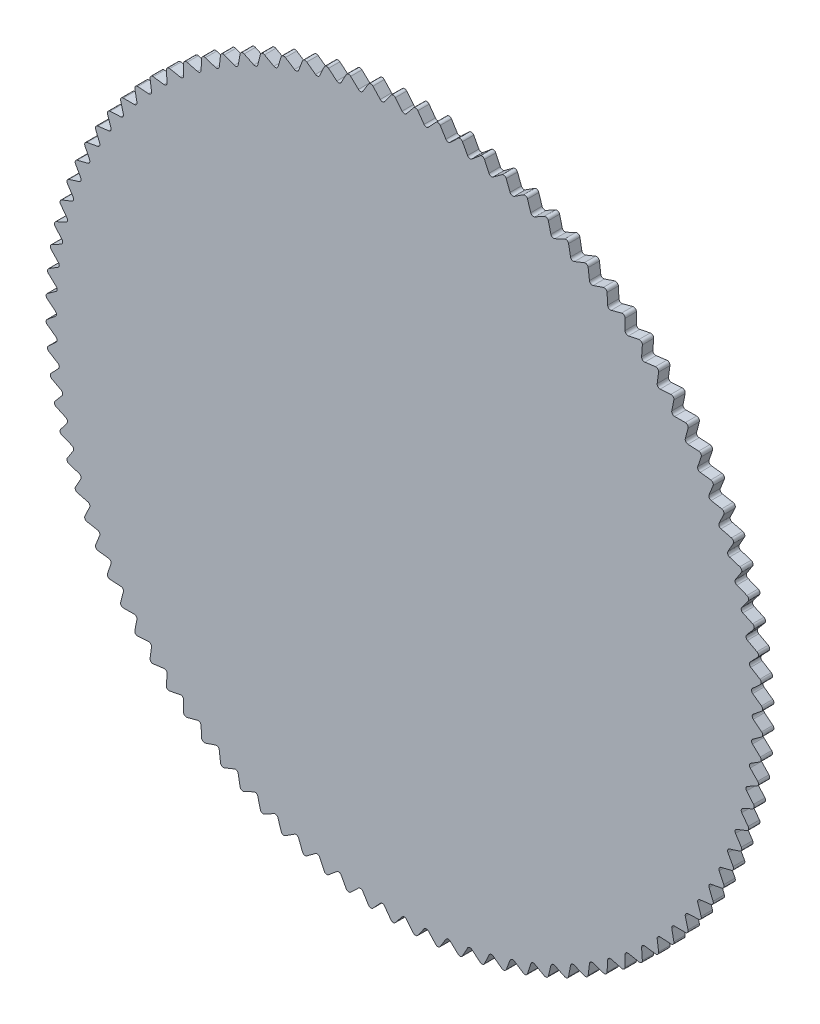
SolidWorks part; units mm, degrees
ref_plane "Front Plane" through (0, 0, 0) normal (0, 0, 1) x (1, 0, 0)
ref_plane "Top Plane" through (0, 0, 0) normal (0, 1, 0) x (1, 0, 0)
ref_plane "Right Plane" through (0, 0, 0) normal (1, 0, 0) x (0, 0, -1)
sketch "Sketch1" plane through (0, 0, 0) normal (0, 0, 1) x (1, 0, 0)
  line L0 (-7.7387, 246.25) -> (7.7387, 246.25) construction
  line L1 (0, 0) -> (0, 246.25) construction
  line L2 (0, 246.25) -> (0, 253.75) construction
  line L5 (-1.5508, 246.9871) -> (-6.3568, 252.8887)
  line L6 (0, 253.75) -> (0, 59.7644) construction
  line L7 (1.5508, 246.9871) -> (6.3568, 252.8887)
  line L8 (0, 0) -> (-7.9705, 253.6248) construction
  line L9 (0, 0) -> (7.9705, 253.6248) construction
  circle A2 centre (0, 0) radius 246.25 construction
  arc A4 (-7.8527, 249.8766) -> (7.8527, 249.8766) centre (0, 0) ccw construction
  circle A5 centre (0, 0) radius 253.75 construction
  arc A6 (-1.5508, 246.9871) -> (1.5508, 246.9871) centre (0, 248.25) ccw
  arc A7 (-6.3568, 252.8887) -> (-7.9705, 253.6248) centre (-7.9077, 251.6258) ccw
  arc A8 (6.3568, 252.8887) -> (7.9705, 253.6248) centre (7.9077, 251.6258) cw
  arc A9 (7.8527, 249.8766) -> (-7.8527, 249.8766) centre (0, 0) ccw construction
  point P13 (7.8527, 249.8766)
  point P14 (0, 0)
  point P16 (-11.2032, 49.5354)
  point P18 (-7.8527, 249.8766)
  point P22 (-2.8499, 46.1457)
  point P23 (-7.8527, 249.8766)
  point P25 (0, 0)
  point P27 (9.6121, 42.5)
  point P28 (-11.4677, 48.6672)
  point P29 (0, 0)
  dimension "D1" = 492.5
  dimension "D4" = 500
  dimension "D3" = 507.5
  dimension "D2" = 2
  dimension "D5" = 15.708
sketch "Sketch2" plane through (0, 0, 0) normal (0, 0, 1) x (1, 0, 0)
  circle A0 centre (0, 0) radius 253.75
  circle A1 centre (0, 0) radius 253.75 construction
extrude "Boss-Extrude1" add sketch "Sketch2" along normal blind 8
sketch "Sketch4" plane through (0, 0, 8) normal (0, 0, 1) x (1, 0, 0)
  line L0 (1.5508, 246.9871) -> (6.3568, 252.8887) construction
  line L1 (-1.5508, 246.9871) -> (-6.3568, 252.8887) construction
  line L2 (1.5508, 246.9871) -> (6.3568, 252.8887)
  line L3 (-1.5508, 246.9871) -> (-6.3568, 252.8887)
  arc A0 (7.9705, 253.6248) -> (6.3568, 252.8887) centre (7.9077, 251.6258) ccw construction
  arc A1 (-1.5508, 246.9871) -> (1.5508, 246.9871) centre (0, 248.25) ccw construction
  arc A2 (-6.3568, 252.8887) -> (-7.9705, 253.6248) centre (-7.9077, 251.6258) ccw construction
  arc A3 (7.9705, 253.6248) -> (6.3568, 252.8887) centre (7.9077, 251.6258) ccw
  arc A4 (-1.5508, 246.9871) -> (1.5508, 246.9871) centre (0, 248.25) ccw
  arc A5 (-6.3568, 252.8887) -> (-7.9705, 253.6248) centre (-7.9077, 251.6258) ccw
  circle A7 centre (0, 0) radius 253.75
  circle A8 centre (0, 0) radius 253.75
  circle M2 centre (0, 0) radius 253.75
  dimension "D1" = 0
extrude "Cut-Extrude3" cut sketch "Sketch4" against normal blind 20 contours A5 L3 A4 L2 A3 M2 region at (0, 250.9634, 8)
ref_axis "Axis1" through (0, 0, 0) along (0, 0, 1)
pattern_circular "CirPattern1" count 100 over 360 about axis through (0, 0, 0) along (0, 0, 1) of "Cut-Extrude3"
equation "\"pitch diameter\" = 500"
equation "\"OD\" = \"pitch diameter\" + ( \"addendum\" )"
equation "\"ID\" = \"pitch diameter\" - ( \"addendum\" )"
equation "\"module\" = 5"
equation "\"number of teeth\"= \"pitch diameter\" / \"module\""
equation "\"reference pitch\"= ( \"pitch diameter\" * pi ) / \"number of teeth\""
equation "\"D1@Sketch1\"=\"ID\""
equation "\"D4@Sketch1\"=\"pitch diameter\""
equation "\"D3@Sketch1\"=\"OD\""
equation "\"addendum\" = \"module\" * 1.5"
equation "\"D5@Sketch1\"=\"reference pitch\""
equation "\"D1@CirPattern1\"=\"number of teeth\""
